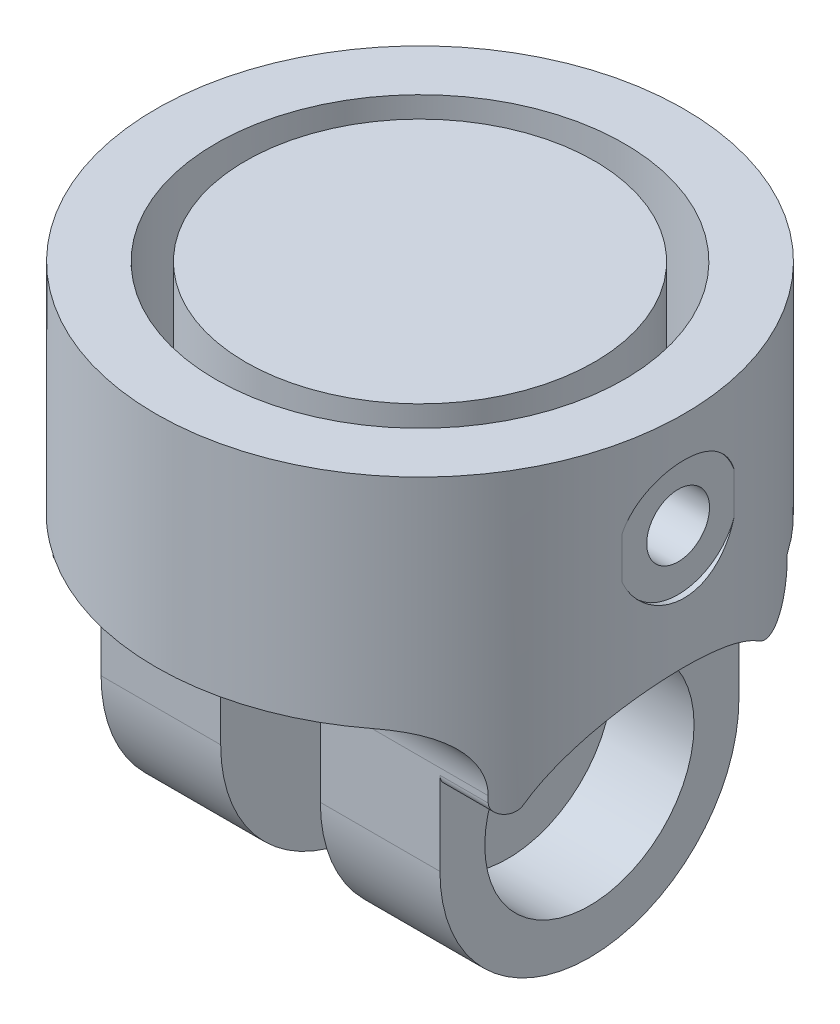
SolidWorks part; units mm, degrees
material "PLA Black"
ref_plane "Front" through (0, 0, 0) normal (0, 0, 1) x (1, 0, 0)
ref_plane "Top" through (0, 0, 0) normal (0, 1, 0) x (1, 0, 0)
ref_plane "Right" through (0, 0, 0) normal (1, 0, 0) x (0, 0, -1)
sketch "Sketch1" plane through (0, 0, 0) normal (0, 1, 0) x (1, 0, 0)
  line L0 (0, 8.75) -> (0, 10.25) construction
  circle A0 centre (0, 0) radius 10.25
  circle A1 centre (0, 0) radius 13.25
  circle A2 centre (0, 0) radius 9.5 construction
  circle A4 centre (0, 0) radius 8.75
  point P11 (0, 9.5)
  dimension "D1" = 1.5
  dimension "D2" = 3
  dimension "D3" = 19
extrude "Boss-Extrude1" add sketch "Sketch1" along normal blind 10 contours A1 A0 | A4 region at (-12.8752, 0, 0) region at (0, 0, 0)
sketch "Sketch3" plane through (0, 0, 0) normal (0, -1, 0) x (1, 0, 0)
  circle A2 centre (0, 0) radius 13.25 construction
  circle A3 centre (0, 0) radius 13.25
extrude "Boss-Extrude2" add sketch "Sketch3" along normal blind 1
sketch "Sketch4" plane through (0, -1, 0) normal (0, -1, 0) x (1, 0, 0)
  line L0 (0, 17.8908) -> (0, -17.0763) construction
  line L1 (2.5, 7.5) -> (8.5, 7.5)
  line L2 (2.5, 7.5) -> (2.5, -7.5)
  line L3 (2.5, -7.5) -> (8.5, -7.5)
  line L4 (8.5, 7.5) -> (8.5, -7.5)
  line L5 (-8.5, 7.5) -> (-8.5, -7.5)
  line L6 (-2.5, -7.5) -> (-8.5, -7.5)
  line L7 (-2.5, 7.5) -> (-2.5, -7.5)
  line L8 (-2.5, 7.5) -> (-8.5, 7.5)
  line L9 (16.8049, 0) -> (-19.8998, 0) construction
  dimension "D1" = 6
  dimension "D2" = 5
  dimension "D3" = 15
extrude "Boss-Extrude3" add sketch "Sketch4" along normal blind 15
sketch "Sketch5" plane through (8.5, 0, 0) normal (1, 0, 0) x (0, 0, -1)
  line L0 (-7.5, -16) -> (-7.5, -1) construction
  line L1 (7.5, -16) -> (7.5, -1) construction
  line L2 (7.5, -8.5) -> (7.5, -17.1619)
  line L3 (7.5, -17.1619) -> (-7.5, -17.1619)
  line L4 (-7.5, -17.1619) -> (-7.5, -8.5)
  arc A0 (-7.5, -8.5) -> (7.5, -8.5) centre (0, -8.5) ccw
  circle A1 centre (0, -8.5) radius 1.75
  dimension "D1" = 3.5
extrude "Cut-Extrude1" cut sketch "Sketch5" against normal through all both and the other way through all
sketch "Sketch6" plane through (8.5, 0, 0) normal (1, 0, 0) x (0, 0, -1)
  circle A0 centre (0, -8.5) radius 5.25
  dimension "D1" = 10.5
extrude "Cut-Extrude2" cut sketch "Sketch6" against normal blind 4.1
mirror "Mirror1" about plane through (0, 0, 0) normal (1, 0, 0) of "Cut-Extrude2"
ref_plane "Plane9" through (2.25, 0, 0) normal (1, 0, 0) x (0, 0, -1)
sketch "Sketch7" plane through (2.25, 0, 0) normal (1, 0, 0) x (0, 0, -1)
  line L0 (3.6, -8.5) -> (3.6, -1) construction
  line L1 (7.5, -1) -> (-7.5, -1) construction
  line L2 (3.488, -7.6091) -> (1.8, -1) construction
  line L3 (3.1582, -6.772) -> (0, -1) construction
  line L4 (1.8, -0.6757) -> (1.8, -1.4422) construction
  line L5 (2.7038, -6.1231) -> (-1.8, -1) construction
  line L6 (2.2518, -5.6912) -> (-3.6, -1) construction
  line L8 (0, -1.6788) -> (0, 0) construction
  line L9 (-8.4824, -8.5) -> (8.712, -8.5) construction
  line L10 (1.8714, -5.4246) -> (-5.4, -1) construction
  line L11 (-3.6, -0.3587) -> (-3.6, -1.6788) construction
  circle A0 centre (0, -8.5) radius 3.6 construction
  dimension "D1" = 7.2
  dimension "D2" = 31.32
  dimension "D3" = 7.5
ref_plane "Plane1" through (2.25, -1, -3.6) normal (0, 1, 0) x (1, 0, 0)
ref_plane "Plane2" through (2.25, -1, -1.8) normal (0, 0.9689, 0.2475) x (1, 0, 0)
ref_plane "Plane3" through (2.25, -1, 0) normal (0, 0.8773, 0.48) x (1, 0, 0)
ref_plane "Plane5" through (2.25, -1, 1.8) normal (0, 0.751, 0.6603) x (1, 0, 0)
ref_plane "Plane6" through (2.25, -1, 3.6) normal (0, 0.6255, 0.7802) x (1, 0, 0)
ref_plane "Plane7" through (2.25, -1, 5.4) normal (0, 0.5198, 0.8543) x (1, 0, 0)
sketch "Sketch8" plane through (2.25, -1, -3.6) normal (0, 1, 0) x (1, 0, 0)
  circle A0 centre (0, 0) radius 0.825
  dimension "D1" = 1.65
extrude "Cut-Extrude5" cut sketch "Sketch8" along normal blind 5.5 and the other way through all
sketch "Sketch9" plane through (2.25, -1, -1.8) normal (0, 0.9689, 0.2475) x (1, 0, 0)
  circle A0 centre (0, 0) radius 0.825
  dimension "D1" = 1.65
extrude "Cut-Extrude3" cut sketch "Sketch9" along normal blind 5.5
sketch "Sketch10" plane through (2.25, -1, 0) normal (0, 0.8773, 0.48) x (1, 0, 0)
  circle A0 centre (0, 0) radius 0.825
  dimension "D1" = 1.65
sketch "Sketch11" plane through (2.25, -1, 1.8) normal (0, 0.751, 0.6603) x (1, 0, 0)
  circle A0 centre (0, 0) radius 0.825
  dimension "D1" = 1.65
sketch "Sketch12" plane through (2.25, -1, 3.6) normal (0, 0.6255, 0.7802) x (1, 0, 0)
  circle A0 centre (0, 0) radius 0.825
  dimension "D1" = 1.65
sketch "Sketch14" plane through (2.25, -1, 5.4) normal (0, 0.5198, 0.8543) x (1, 0, 0)
  circle A0 centre (0, 0) radius 0.825
  dimension "D1" = 1.65
extrude "Cut-Extrude6" cut sketch "Sketch10" along normal blind 5.5 and the other way through all
extrude "Cut-Extrude7" cut sketch "Sketch11" along normal blind 5.5 and the other way through all contours A0
extrude "Cut-Extrude8" cut sketch "Sketch12" along normal blind 5.5 and the other way through all contours A0
extrude "Cut-Extrude9" cut sketch "Sketch14" along normal blind 5.5 and the other way through all contours A0
ref_plane "Plane8" through (13.25, 0, 0) normal (1, 0, 0) x (0, 0, -1)
hole_wizard "Tap Drill for M3 Helicoil1" positions "Sketch17" profile "Sketch18" hole size "M3x0.5" standard "DIN"
sketch "Sketch17" plane through (13.25, 0, 0) normal (1, 0, 0) x (0, 0, -1)
  line L0 (-22.2973, 5) -> (18.0703, 5) construction
  line L4 (0, 12.2732) -> (0, -5.3405) construction
  line L6 (-7.5, -8.5) -> (-7.5, -1) construction
  line L7 (7.5, -8.5) -> (7.5, -1) construction
  line L8 (13.25, 10) -> (-13.25, 10) construction
  line L9 (10.25, 0) -> (-10.25, 0) construction
  point P0 (0, 5)
sketch "Sketch18" plane through (13.25, 5, 0) normal (0, 1, 0) x (0, 0, -1)
  line L0 (0, 0) -> (0, 6.9464)
  line L1 (0, 6.9464) -> (1.575, 6)
  line L2 (1.575, 6) -> (1.575, 0)
  line L5 (1.575, 0) -> (0, 0)
  line L10 (0, 6.9464) -> (-1.575, 6) construction
  line L11 (0, -6.35) -> (0, 107.95) construction
  dimension "Hole Dia." = 3.15
  dimension "Hole Depth" = 6
  dimension "Drill Angle" = 118
sketch "Sketch20" plane through (13.25, 0, 0) normal (1, 0, 0) x (0, 0, -1)
  circle A0 centre (0, 5) radius 3
  dimension "D1" = 6
extrude "Cut-Extrude10" cut sketch "Sketch20" against normal blind 0.3
sketch "Sketch21" plane through (8.5, 0, 0) normal (1, 0, 0) x (0, 0, -1)
  line L0 (7.5, -1) -> (-7.5, -1) construction
  line L1 (7.5, -0.1252) -> (7.5, -1.1767)
  line L2 (0.9244, -19.0662) -> (-4.8209, -14.2453) construction
  line L3 (0, 5.2718) -> (0, -9.2894) construction
  line L4 (0, 10) -> (0, -1) construction
  line L5 (-7.5, -0.1252) -> (-7.5, -4.3226)
  line L6 (7.5, -0.1252) -> (-7.5, -0.1252)
  line L7 (-7.5, -8.5) -> (-7.5, -1) construction
  line L8 (7.5, -8.5) -> (7.5, -1) construction
  line L9 (0, -1) -> (9.4693, -4.4465) construction
  line L10 (0, -1) -> (1.6171, -0.0664) construction
  line L11 (4.6128, -2.5863) -> (7.5, -1.1767) construction
  line L12 (10.5662, -7.5756) -> (4.8209, -2.7547) construction
  line L13 (-4.8209, -14.2453) -> (4.8209, -2.7547) construction
  line L14 (10.5662, -7.5756) -> (0.9244, -19.0662) construction
  arc A0 (-6.4204, -4.6233) -> (4.6128, -2.5863) centre (0, -8.5) cw
  arc A1 (-6.4204, -4.6233) -> (-7.5, -4.3226) centre (-6.9183, -4.3226) cw
  arc A2 (7.5, -1.1767) -> (4.6128, -2.5863) centre (5.7123, -1.1767) cw
  circle A3 centre (0, -8.5) radius 1.75 construction
  arc A4 (-4.8209, -14.2453) -> (4.8209, -2.7547) centre (0, -8.5) cw construction
  dimension "D1" = 30
  dimension "D3" = 7.5
  dimension "D2" = 50
  dimension "D4" = 15
extrude "Boss-Extrude4" add sketch "Sketch21" along normal up to surface (2.423 mm away) up to face at (13.0965, 5, 0)
mirror "Mirror2" about plane through (0, 0, 0) normal (1, 0, 0) of "Boss-Extrude4", "Tap Drill for M3 Helicoil1", "Cut-Extrude10"
fillet "Fillet1" radius 3 2 edges at (-6.7115, -1, 7.5) (6.7115, -1, 7.5)
equation "\"knee_angle\"= 70"
equation "\"ankle_angle\" = 80"
equation "\"hip_angle\" = 40"
equation "\"spring_ankle_parallel_arm_diameter\"= 1.5"
equation "\"spring_ankle_parallel_arm_length\"= 13"
equation "\"spring_ankle_parallel_intern_diameter\"= 5.7"
equation "\"spring_ankle_parallel_angle\"= \"ankle_angle\""
equation "\"spring_ankle_parallel_turns\"= 3"
equation "\"spring_ankle_parallel_pitch\"= \"spring_ankle_parallel_arm_diameter\" * 1.01"
equation "\"spring_ankle_parallel_cutting_distance\"= (1-\"spring_ankle_parallel_angle\" / 360) * \"spring_ankle_parallel_pitch\""
equation "\"spring_ankle_serial_arm_diameter\"= 1.91"
equation "\"spring_ankle_serial_arm_length\"= 10"
equation "\"spring_ankle_serial_intern_diameter\"= 5.7"
equation "\"spring_ankle_serial_angle\"= \"90\""
equation "\"spring_ankle_serial_turns\"= 3"
equation "\"spring_ankle_serial_pitch\"= \"spring_ankle_serial_arm_diameter\" * 1.01"
equation "\"spring_ankle_serial_cutting_distance\"= (1-\"spring_ankle_serial_angle\" / 360) * \"spring_ankle_serial_pitch\""
equation "\"spring_knee_parallel_arm_diameter\"= 1.5"
equation "\"spring_knee_parallel_arm_length\"= 13"
equation "\"spring_knee_parallel_intern_diameter\"= 5.7"
equation "\"spring_knee_parallel_angle\"= -\"knee_angle\" + 90"
equation "\"spring_knee_parallel_turns\"= 3"
equation "\"spring_knee_parallel_pitch\"= \"spring_knee_parallel_arm_diameter\" * 1.01"
equation "\"spring_knee_parallel_cutting_distance\"= (1-(\"spring_knee_parallel_angle\") / 360) * \"spring_knee_parallel_pitch\""
equation "\"spring_knee_serial_arm_diameter\"= 1.91"
equation "\"spring_knee_serial_arm_length\"= 10"
equation "\"spring_knee_serial_intern_diameter\"= 5.7"
equation "\"spring_knee_serial_angle\"= \"90\""
equation "\"spring_knee_serial_turns\"= 3"
equation "\"spring_knee_serial_pitch\"= \"spring_knee_serial_arm_diameter\" * 1.01"
equation "\"spring_knee_serial_cutting_distance\"= (1-\"spring_knee_serial_angle\" / 360) * \"spring_knee_serial_pitch\""
equation "\"spring_ankle_parallel_nominal_diameter\"= \"spring_ankle_parallel_arm_diameter\" + \"spring_ankle_parallel_intern_diameter\""
equation "\"spring_ankle_serial_nominal_diameter\"= \"spring_ankle_serial_arm_diameter\" + \"spring_ankle_serial_intern_diameter\""
equation "\"spring_knee_parallel_nominal_diameter\"= \"spring_knee_parallel_arm_diameter\" + \"spring_knee_parallel_intern_diameter\""
equation "\"spring_knee_serial_nominal_diameter\"= \"spring_knee_serial_arm_diameter\" + \"spring_knee_serial_intern_diameter\""
equation "\"D1@Sketch7\"=\"spring_ankle_parallel_nominal_diameter\""
equation "\"D1@Sketch8\"=\"spring_ankle_parallel_arm_diameter\"*1.1"
equation "\"D1@Sketch9\"=\"spring_ankle_parallel_arm_diameter\"*1.1"
equation "\"D1@Sketch10\"=\"spring_ankle_parallel_arm_diameter\"*1.1"
equation "\"D1@Sketch11\"=\"spring_ankle_parallel_arm_diameter\"*1.1"
equation "\"D1@Sketch12\"=\"spring_ankle_parallel_arm_diameter\"*1.1"
equation "\"D1@Sketch14\"=\"spring_ankle_parallel_arm_diameter\"*1.1"
equation "\"D1@Cut-Extrude3\"=\"spring_ankle_parallel_arm_length\"-\"axis_structure_distance\""
equation "\"axis_structure_distance\"= 7.5"
equation "\"D1@Cut-Extrude5\"=\"spring_ankle_parallel_arm_length\"-\"axis_structure_distance\""
equation "\"D1@Cut-Extrude6\"=\"spring_ankle_parallel_arm_length\"-\"axis_structure_distance\""
equation "\"D1@Cut-Extrude7\"=\"spring_ankle_parallel_arm_length\"-\"axis_structure_distance\""
equation "\"D1@Cut-Extrude8\"=\"spring_ankle_parallel_arm_length\"-\"axis_structure_distance\""
equation "\"D1@Cut-Extrude9\"=\"spring_ankle_parallel_arm_length\"-\"axis_structure_distance\""
equation "\"D1@Boss-Extrude3\"=\"axis_structure_distance\"*2"
equation "\"ankle_angle_max\" = 120"
equation "\"ankle_angle_min\" = 50"
equation "\"knee_angle_max\" = 120"
equation "\"knee_angle_min\" = 0"
equation "\"hip_angle_max\" = 90"
equation "\"hip_angle_min\" = -60"
equation "\"D1@Sketch21\"=\"ankle_angle_max\"-90"
equation "\"D2@Sketch21\"=\"ankle_angle_min\""
equation "\"D1@Plane9\"=(\"spring_ankle_parallel_arm_diameter\"*\"spring_ankle_parallel_turns\")/2"
